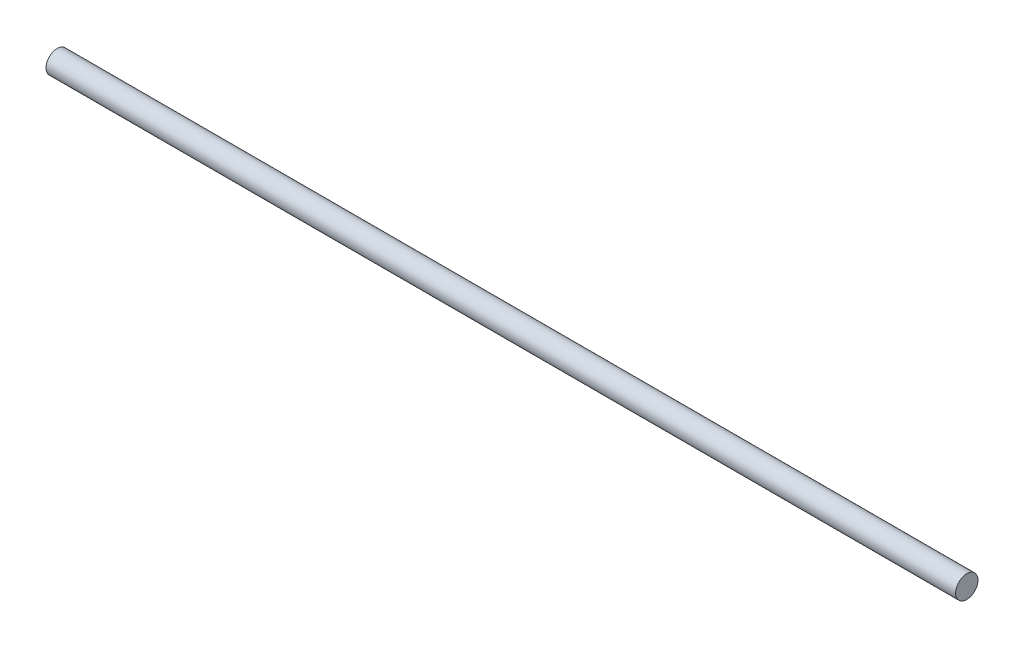
SolidWorks part; units mm, degrees
ref_plane "Front Plane" through (0, 0, 0) normal (0, 0, 1) x (1, 0, 0)
ref_plane "Top Plane" through (0, 0, 0) normal (0, 1, 0) x (1, 0, 0)
ref_plane "Right Plane" through (0, 0, 0) normal (1, 0, 0) x (0, 0, -1)
sketch "Sketch1" plane through (0, 0, 0) normal (1, 0, 0) x (0, 0, -1)
  circle A0 centre (0, 0) radius 4
  dimension "D1" = 8
extrude "Boss-Extrude1" add sketch "Sketch1" along normal blind 325
